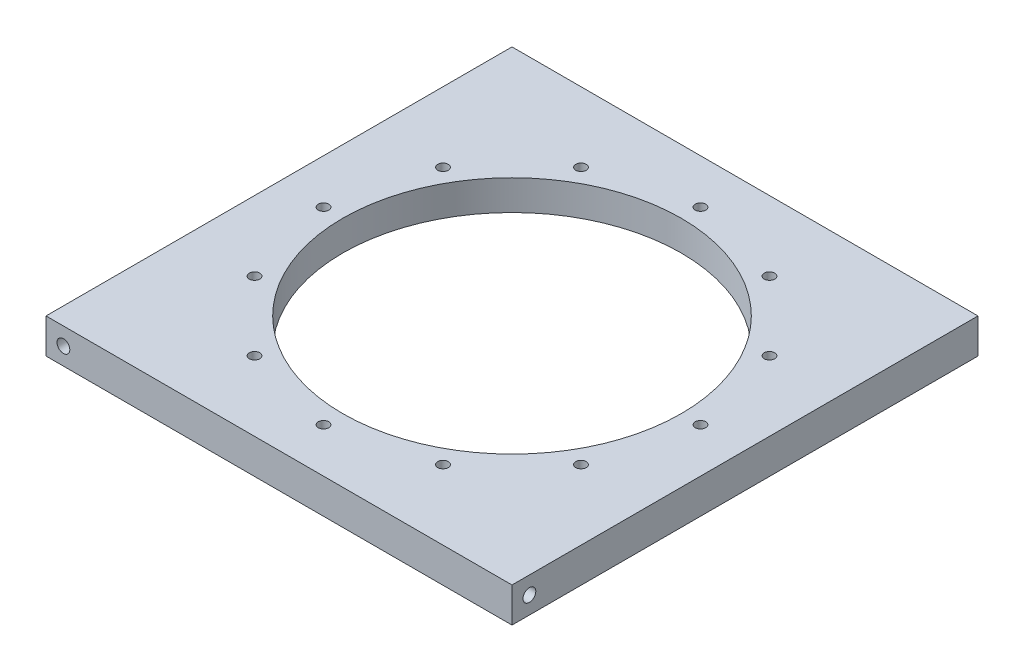
SolidWorks part; units mm, degrees
material "6061-T6 (SS)"
ref_plane "Front Plane" through (0, 0, 0) normal (0, 0, 1) x (1, 0, 0)
ref_plane "Top Plane" through (0, 0, 0) normal (0, 1, 0) x (1, 0, 0)
ref_plane "Right Plane" through (0, 0, 0) normal (1, 0, 0) x (0, 0, -1)
sketch "Sketch1" plane through (0, 0, 0) normal (0, 1, 0) x (1, 0, 0)
  line L5 (0, 0) -> (127.635, 0)
  line L6 (0, 0) -> (0, 127.635)
  line L7 (0, 127.635) -> (127.635, 127.635)
  line L8 (127.635, 0) -> (127.635, 127.635)
  dimension "D1" = 127.635
  dimension "D2" = 127.635
extrude "Boss-Extrude1" add sketch "Sketch1" along normal blind 9.525 contours L5 L8 L7 L6
sketch "Sketch5" plane through (0, 9.525, 0) normal (0, 1, 0) x (1, 0, 0)
  line L0 (63.8175, 0) -> (63.8175, 127.635) construction
  line L3 (0, 0) -> (127.635, 0) construction
  line L8 (0, 127.635) -> (127.635, 127.635) construction
  circle A0 centre (63.8175, 63.8175) radius 46.355
  dimension "D1" = 92.71
extrude "Cut-Extrude1" cut sketch "Sketch5" against normal blind 9.525 contours L0 A0 | A0 L0
sketch "Sketch6" plane through (127.635, 0, 0) normal (1, 0, 0) x (0, 0, -1)
  circle A0 centre (4.7625, 4.7625) radius 1.7526
  dimension "D1" = 3.5052
extrude "6-32 hole1" cut sketch "Sketch6" against normal blind 6.35
sketch "Sketch7" plane through (0, 0, -127.635) normal (0, 0, -1) x (-1, 0, 0)
  circle A0 centre (-122.8725, 4.7625) radius 1.7526
  dimension "D1" = 3.5052
sketch "Sketch8" plane through (0, 0, 0) normal (-1, 0, 0) x (0, 0, 1)
  circle A0 centre (-122.8725, 4.7625) radius 1.7526
  dimension "D1" = 3.5052
sketch "Sketch9" plane through (0, 0, 0) normal (0, 0, 1) x (1, 0, 0)
  circle A0 centre (4.7625, 4.7625) radius 1.7526
  dimension "D1" = 3.5052
extrude "6-32 hole2" cut sketch "Sketch7" against normal blind 6.35
extrude "6-32 hole3" cut sketch "Sketch8" against normal blind 6.35
extrude "6-32 hole4" cut sketch "Sketch9" against normal blind 6.35
sketch "Sketch10" plane through (0, 0, 0) normal (0, -1, 0) x (1, 0, 0)
  circle A0 centre (63.8175, -63.8175) radius 56.4198
  dimension "D1" = 112.8395
extrude "Cut-Extrude2" cut sketch "Sketch10" against normal blind 1.27
sketch "Sketch11" plane through (0, 9.525, 0) normal (0, 1, 0) x (1, 0, 0)
  line L0 (63.8175, 63.8175) -> (63.8175, 115.443) construction
  circle A0 centre (63.8175, 115.443) radius 1.4351
  dimension "D2" = 2.8702
  dimension "D1" = 51.6255
extrude "Cut-Extrude3" cut sketch "Sketch11" against normal through all contours A0
pattern_circular "CirPattern1" count 12 over 360 about axis through (63.8175, 9.525, -63.8175) along (0, 1, 0) of "Cut-Extrude3"
